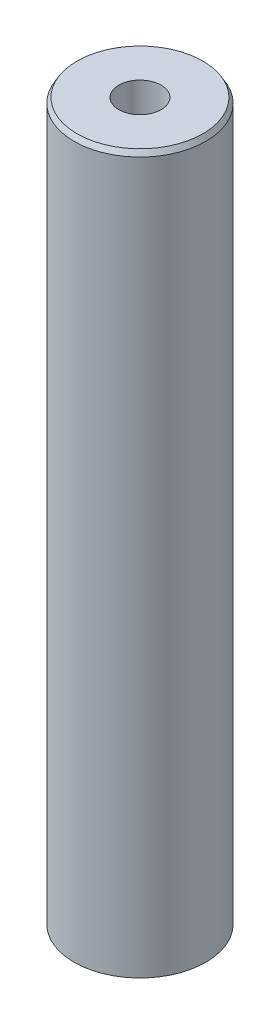
SolidWorks part; units mm, degrees
ref_plane "Front Plane" through (0, 0, 0) normal (0, 0, 1) x (1, 0, 0)
ref_plane "Top Plane" through (0, 0, 0) normal (0, 1, 0) x (1, 0, 0)
ref_plane "Right Plane" through (0, 0, 0) normal (1, 0, 0) x (0, 0, -1)
sketch "Sketch1" plane through (0, 0, 0) normal (0, 1, 0) x (1, 0, 0)
  circle A0 centre (0, 0) radius 55
  dimension "SHAFT_OD" = 110
extrude "Boss-Extrude1" add sketch "Sketch1" along normal blind 600
sketch "Sketch2" plane through (0, 0, 0) normal (0, 1, 0) x (1, 0, 0)
  circle A0 centre (0, 0) radius 17.7145
  dimension "BORE_D" = 35.4289
extrude "Cut-Extrude1" cut sketch "Sketch2" along normal through all
chamfer "Chamfer1" distance 4.2585 angle 30 2 edges at (0, 600, 55) (0, 0, 55) first distance on face at (0, 600, 55) first distance on face at (0, 0, 17.7145)
